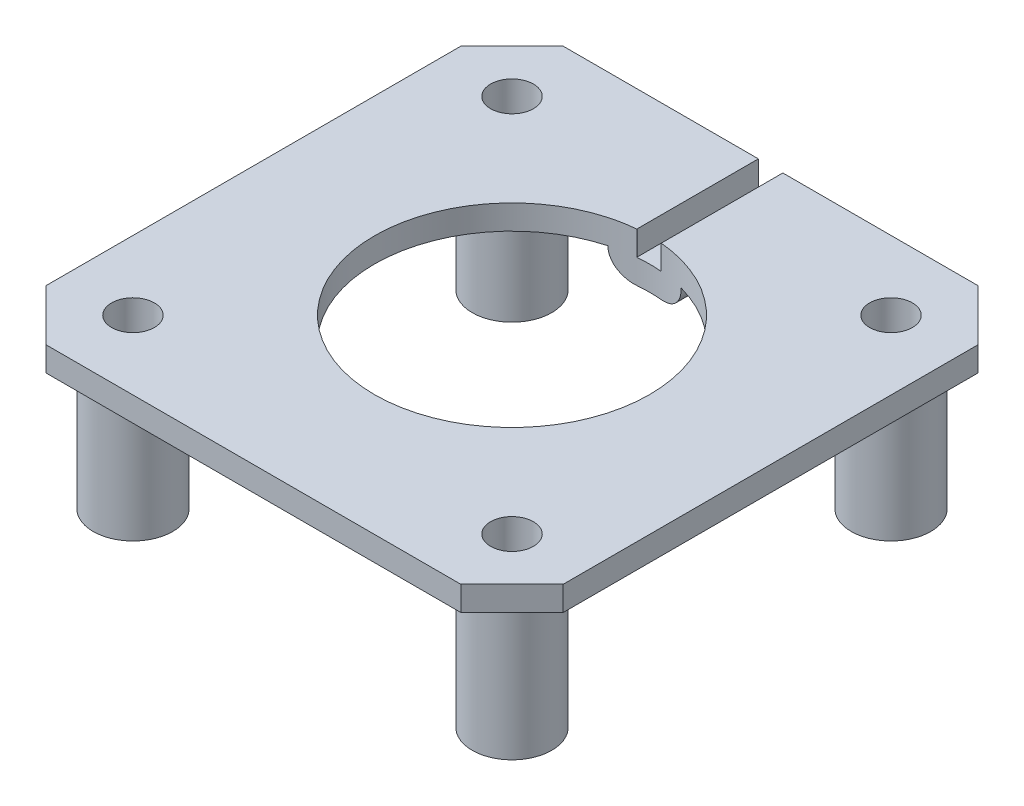
SolidWorks part; units mm, degrees
ref_plane "Front Plane" through (0, 0, 0) normal (0, 0, 1) x (1, 0, 0)
ref_plane "Top Plane" through (0, 0, 0) normal (0, 1, 0) x (1, 0, 0)
ref_plane "Right Plane" through (0, 0, 0) normal (1, 0, 0) x (0, 0, -1)
sketch "Sketch1" plane through (0, 0, 0) normal (0, 1, 0) x (1, 0, 0)
  circle A4 centre (-15.5, 15.5) radius 3.25
  dimension "D3" = 6.5
extrude "Boss-Extrude1" add sketch "Sketch1" along normal blind 13.7
mirror "Mirror2" about plane through (0, 0, 0) normal (1, 0, 0) of bodies 101
mirror "Mirror3" about plane through (0, 0, 0) normal (0, 0, 1) of bodies 101 102
sketch "Sketch2" plane through (0, 13.7, 0) normal (0, 1, 0) x (1, 0, 0)
  line L1 (-21.15, 21.15) -> (21.15, 21.15)
  line L2 (-21.15, 21.15) -> (-21.15, -21.15)
  line L3 (-21.15, -21.15) -> (21.15, -21.15)
  line L4 (21.15, 21.15) -> (21.15, -21.15)
  line L5 (-21.15, 21.15) -> (21.15, -21.15) construction
  line L6 (-21.15, -21.15) -> (21.15, 21.15) construction
  circle A0 centre (0, 0) radius 11.25
  dimension "D1" = 22.5
  dimension "D4" = 42.3
extrude "Boss-Extrude2" add sketch "Sketch2" against normal blind 2
sketch "Sketch3" plane through (0, 13.7, 0) normal (0, 1, 0) x (1, 0, 0)
  line L0 (-16.9631, 21.15) -> (-21.15, 16.9631)
  line L1 (21.15, 21.15) -> (-21.15, 21.15) construction
  line L2 (-21.15, 21.15) -> (-21.15, -21.15) construction
  line L3 (16.9631, -21.15) -> (21.15, -16.9631)
  line L4 (-21.15, -21.15) -> (21.15, -21.15) construction
  line L5 (21.15, -21.15) -> (21.15, 21.15) construction
  line L6 (-21.15, 16.9631) -> (-21.15, 21.15)
  line L7 (-21.15, 21.15) -> (-16.9631, 21.15)
  line L8 (21.15, -16.9631) -> (21.15, -21.15)
  line L9 (21.15, -21.15) -> (16.9631, -21.15)
  dimension "D1" = 45
  dimension "D2" = 53.9
extrude "Cut-Extrude1" cut sketch "Sketch3" against normal through all
mirror "Mirror4" about plane through (0, 0, 0) normal (0, 0, 1) of "Cut-Extrude1"
sketch "Sketch4" plane through (0, 0, 0) normal (0, -1, 0) x (1, 0, 0)
  circle A1 centre (15.5, -15.5) radius 3.25 construction
  circle A3 centre (15.5, -15.5) radius 1.75
  dimension "D1" = 3.5
extrude "Cut-Extrude2" cut sketch "Sketch4" against normal through all
mirror "Mirror5" about plane through (0, 0, 0) normal (1, 0, 0) of "Cut-Extrude2"
mirror "Mirror6" about plane through (0, 0, 0) normal (0, 0, 1) of "Mirror5"
sketch "Sketch6" plane through (0, 11.7, 0) normal (0, -1, 0) x (1, 0, 0)
  line L0 (0, -21.15) -> (0, -11.25) construction
  line L1 (16.9631, -21.15) -> (-16.9631, -21.15) construction
  line L2 (-3, -21.15) -> (-3, -10.8426)
  line L3 (3, -21.15) -> (3, -10.8426)
  line L4 (3, -21.15) -> (-3, -21.15)
  circle A0 centre (0, 0) radius 11.25 construction
  arc A3 (-3, -10.8426) -> (3, -10.8426) centre (0, 0) ccw
  point P7 (0, -18.325)
  point P12 (0, 0)
  point P13 (0, 0)
  point P15 (0, 0)
  dimension "D1" = 6
  dimension "D2" = 3
extrude "Boss-Extrude3" add sketch "Sketch6" along normal blind 2
sketch "Sketch7" plane through (0, 13.7, 0) normal (0, 1, 0) x (1, 0, 0)
  line L0 (0, 11.25) -> (0, 21.15) construction
  line L1 (16.9631, 21.15) -> (-16.9631, 21.15) construction
  line L2 (-1, 11.25) -> (-1, 21.15)
  line L3 (1, 11.25) -> (1, 21.15)
  circle A0 centre (0, 0) radius 11.25 construction
  arc A1 (-1, 11.25) -> (1, 11.25) centre (0, 11.25) ccw
  arc A2 (1, 21.15) -> (-1, 21.15) centre (0, 21.15) ccw
  point P6 (0, 16.2)
  dimension "D1" = 2
extrude "Cut-Extrude3" cut sketch "Sketch7" against normal blind 2
fillet "Fillet1" radius 2 2 edges at (3, 9.7, -15.9963) (-3, 9.7, -15.9963)
